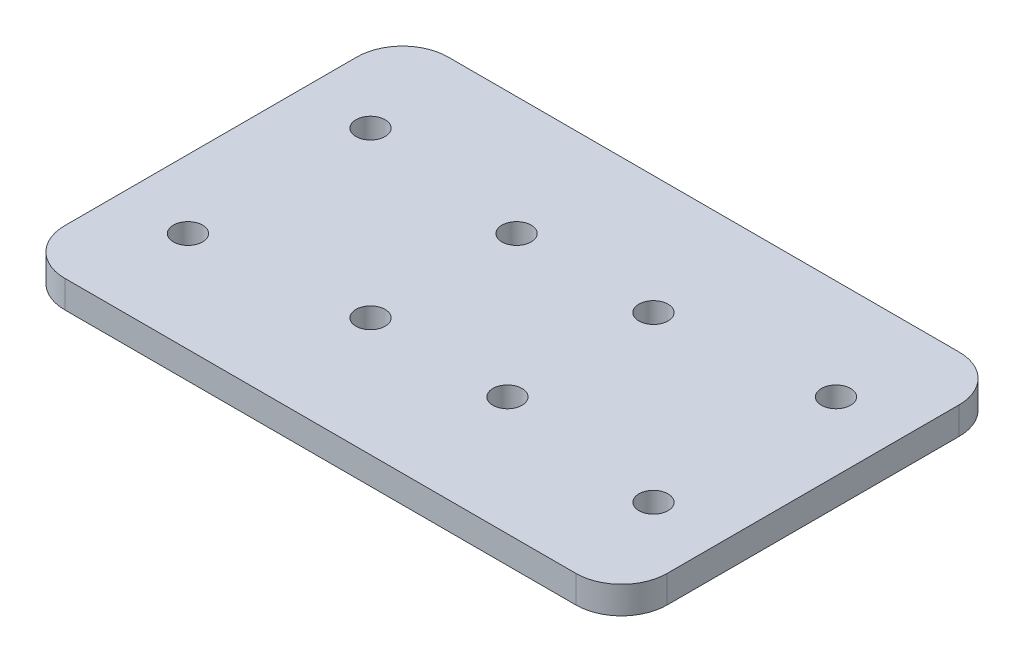
SolidWorks part; units mm, degrees
material "Carbon Fiber"
ref_plane "Front Plane" through (0, 0, 0) normal (0, 0, 1) x (1, 0, 0)
ref_plane "Top Plane" through (0, 0, 0) normal (0, 1, 0) x (1, 0, 0)
ref_plane "Right Plane" through (0, 0, 0) normal (1, 0, 0) x (0, 0, -1)
sketch "Sketch1" plane through (0, 0, 0) normal (0, 1, 0) x (1, 0, 0)
  line L0 (7.5, 42) -> (7.5, 0) construction
  line L1 (0, 0) -> (66, 0)
  line L2 (0, 0) -> (0, 42)
  line L3 (0, 42) -> (66, 42)
  line L4 (66, 0) -> (66, 42)
  line L5 (33, 42) -> (33, 0) construction
  line L6 (66, 21) -> (0, 21) construction
  circle A0 centre (7.5, 31) radius 1.6
  circle A1 centre (7.5, 11) radius 1.6
  circle A2 centre (58.5, 11) radius 1.6
  circle A3 centre (58.5, 31) radius 1.6
  dimension "D3" = 20
  dimension "D4" = 3.2
  dimension "D1" = 66
  dimension "D2" = 42
  dimension "D5" = 7.5
extrude "Boss-Extrude1" add sketch "Sketch1" along normal blind 3
sketch "Sketch2" plane through (0, 3, 0) normal (0, 1, 0) x (1, 0, 0)
  line L0 (33, 29) -> (33, 13) construction
  line L1 (25.5, 13) -> (40.5, 13) construction
  line L2 (25.5, 13) -> (25.5, 29) construction
  line L3 (25.5, 29) -> (40.5, 29) construction
  line L4 (40.5, 13) -> (40.5, 29) construction
  line L5 (0, 21) -> (66, 21) construction
  line L6 (0, 42) -> (0, 0) construction
  line L7 (66, 0) -> (66, 42) construction
  circle A0 centre (40.5, 29) radius 1.6
  circle A1 centre (40.5, 13) radius 1.6
  circle A2 centre (25.5, 13) radius 1.6
  circle A3 centre (25.5, 29) radius 1.6
  point P12 (33, 21)
  dimension "D1" = 3.2
  dimension "D2" = 16
  dimension "D3" = 15
extrude "Cut-Extrude1" cut sketch "Sketch2" against normal through all
fillet "Fillet1" radius 5 4 edges at (0, 1.5, -42) (66, 1.5, -42) (66, 1.5, 0) (0, 1.5, 0)
